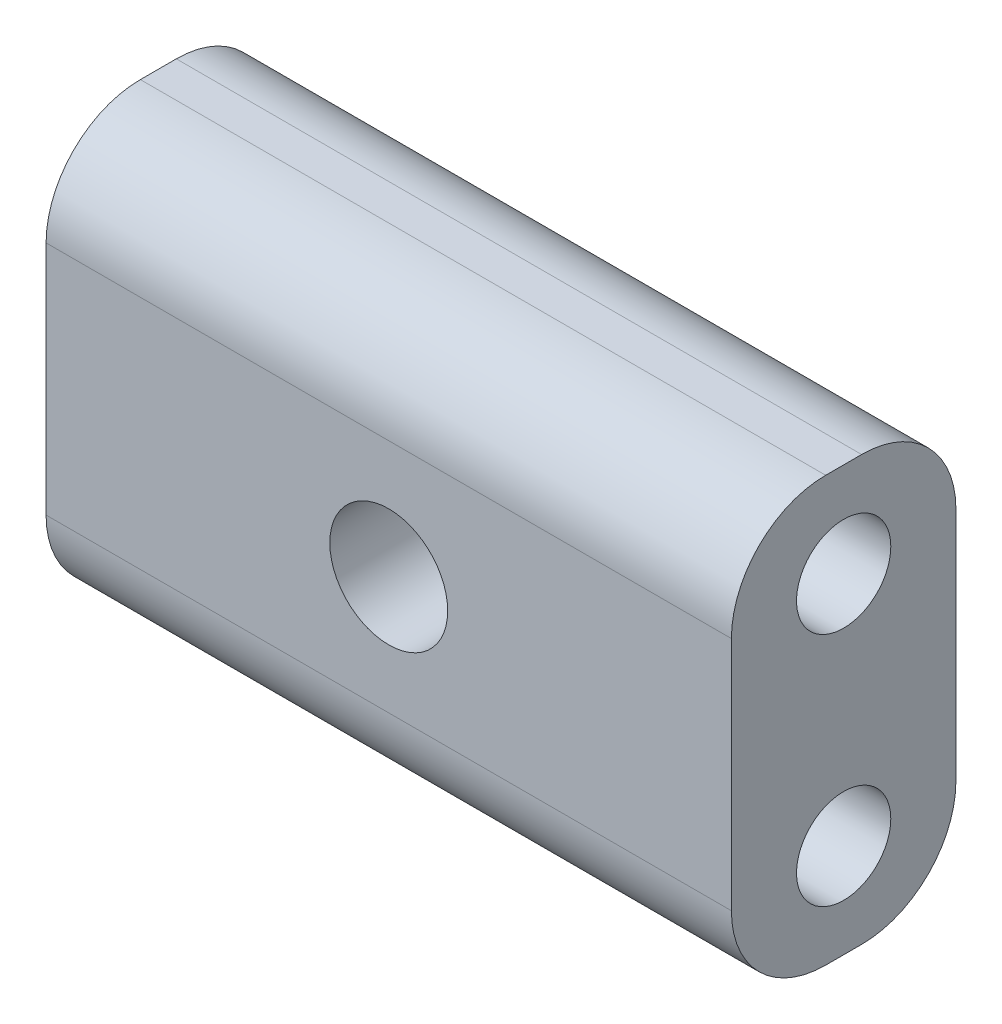
SolidWorks part; units mm, degrees
material "6061 Alloy"
ref_plane "Front Plane" through (0, 0, 0) normal (0, 0, 1) x (1, 0, 0)
ref_plane "Top Plane" through (0, 0, 0) normal (0, 1, 0) x (1, 0, 0)
ref_plane "Right Plane" through (0, 0, 0) normal (1, 0, 0) x (0, 0, -1)
sketch "Sketch1" plane through (0, 0, 0) normal (0, 0, 1) x (1, 0, 0)
  line L1 (-14.5375, 9) -> (14.5375, 9)
  line L2 (-14.5375, 9) -> (-14.5375, -9)
  line L3 (-14.5375, -9) -> (14.5375, -9)
  line L4 (14.5375, 9) -> (14.5375, -9)
  line L5 (0, -9) -> (0, 9) construction
  line L6 (-14.5375, 0) -> (14.5375, 0) construction
  point P0 (0, 0)
  dimension "D1" = 29.075
  dimension "D2" = 18
extrude "3/8" add sketch "Sketch1" along normal blind 9.525
sketch "Sketch2" plane through (-14.5375, 0, 0) normal (-1, 0, 0) x (0, 0, 1)
  line L0 (4.7625, 9) -> (4.7625, -9) construction
  line L1 (9.525, 9) -> (0, 9) construction
  line L2 (9.525, -9) -> (0, -9) construction
  line L3 (0, 0) -> (9.525, 0) construction
  line L4 (9.525, 9) -> (9.525, -9) construction
  circle A0 centre (4.7625, 5) radius 2
  circle A1 centre (4.7625, -5) radius 2
  dimension "D2" = 4
  dimension "D1" = 5
extrude "M4_DRILL" cut sketch "Sketch2" against normal blind 8
sketch "Sketch3" plane through (14.5375, 0, 0) normal (1, 0, 0) x (0, 0, -1)
  circle A0 centre (-4.7625, -5) radius 2 construction
  circle A1 centre (-4.7625, 5) radius 2 construction
  circle A2 centre (-4.7625, -5) radius 2
  circle A3 centre (-4.7625, 5) radius 2
extrude "Cut-Extrude2" cut sketch "Sketch3" against normal blind 8
sketch "Sketch5" plane through (0, 0, 0) normal (0, 0, -1) x (-1, 0, 0)
  circle A0 centre (0, 0) radius 2.5
  dimension "D1" = 5
extrude "M5_DRILL" cut sketch "Sketch5" against normal up to surface (9.525 mm away) up to face at (0, 0, 9.525)
fillet "Fillet1" radius 4 4 edges at (0, -9, 9.525) (0, -9, 0) (0, 9, 9.525) (0, 9, 0)
